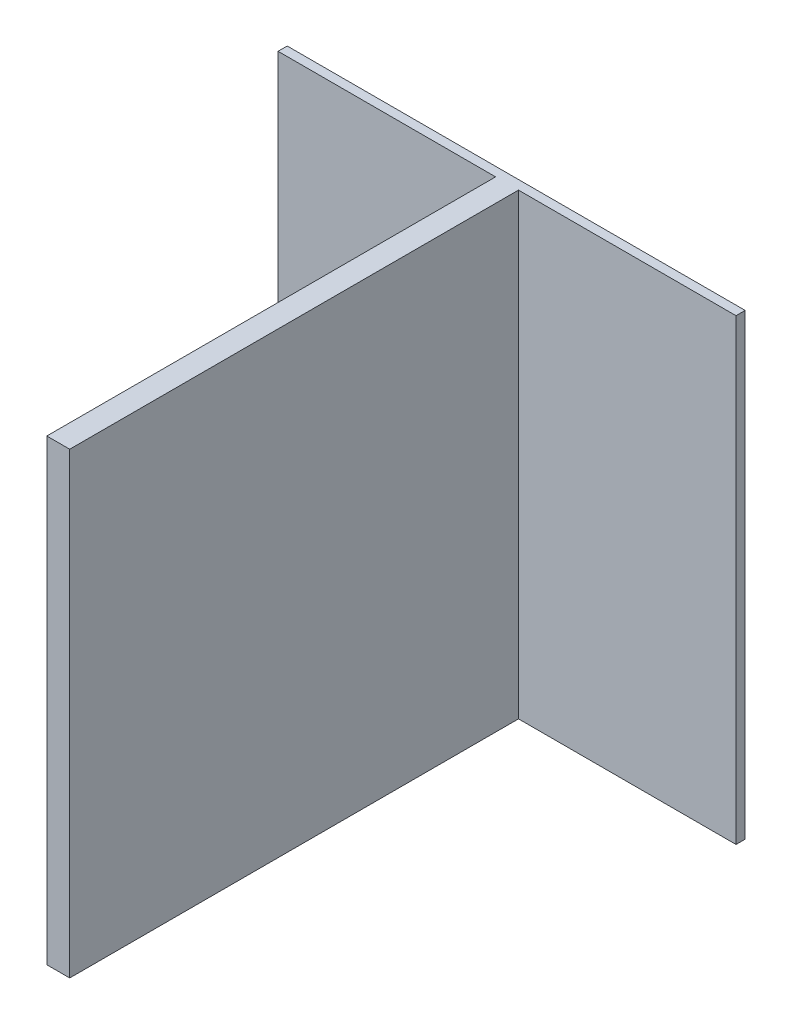
SolidWorks part; units mm, degrees
ref_plane "Płaszczyzna przednia" through (0, 0, 0) normal (0, 0, 1) x (1, 0, 0)
ref_plane "Płaszczyzna górna" through (0, 0, 0) normal (0, 1, 0) x (1, 0, 0)
ref_plane "Płaszczyzna prawa" through (0, 0, 0) normal (1, 0, 0) x (0, 0, -1)
sketch "Szkic1" plane through (0, 0, 0) normal (0, 0, 1) x (1, 0, 0)
  line L0 (0, 0) -> (100, 0)
  line L1 (0, 0) -> (-100, 0)
  line L2 (0, 0) -> (0, 100)
  line L3 (0, 0) -> (0, -100)
  line L4 (0, 100) -> (100, 100)
  line L5 (100, 100) -> (100, 0)
  line L6 (100, -100) -> (0, -100)
  line L7 (100, 0) -> (100, -100)
  line L8 (0, 100) -> (-100, 100)
  line L9 (-100, 100) -> (-100, 0)
  line L10 (-100, -100) -> (-100, 0)
  line L11 (0, -100) -> (-100, -100)
  dimension "D1" = 100
  dimension "D2" = 100
  dimension "D3" = 100
  dimension "D4" = 100
  dimension "D5" = 100
  dimension "D6" = 100
  dimension "D7" = 100
  dimension "D8" = 100
  dimension "D9" = 100
  dimension "D10" = 100
  dimension "D11" = 100
extrude "Dodanie-wyciągnięcie1" add sketch "Szkic1" along normal blind 4 contours L8 L9 L1 L2 | L5 L4 L2 L0 | L7 L0 L3 L6 | L11 L3 L1 L10 region at (50, 50, 0) region at (-50, -50, 0) region at (-50, 50, 0) region at (50, -50, 0)
sketch "Szkic2" plane through (0, 0, 4) normal (0, 0, 1) x (1, 0, 0)
  line L0 (0, 100) -> (0, -100)
  line L1 (100, 100) -> (-100, 100) construction
  line L2 (100, -100) -> (-100, -100) construction
  line L3 (0, 0) -> (5, 0)
  line L4 (0, 0) -> (-5, 0)
  line L5 (5, 0) -> (5, 100)
  line L6 (5, 100) -> (5, -100)
  line L7 (-5, 0) -> (-5, 100)
  line L8 (-5, 0) -> (-5, -100)
  line L9 (-5, -100) -> (5, -100)
  line L10 (5, 100) -> (-5, 100)
  line M9 (-100, -100) -> (100, -100)
  line M11 (100, 100) -> (-100, 100)
  dimension "D1" = 5
  dimension "D2" = 5
  dimension "D3" = 10
  dimension "D4" = 100
  dimension "D5" = 100
  dimension "D6" = 100
  dimension "D7" = 200
  dimension "D8" = 10
extrude "Dodanie-wyciągnięcie2" add sketch "Szkic2" along normal blind 196 contours L7 L4 L0 M11 | L3 L5 L0 M11 | L4 L8 L0 M9 | L6 L3 L0 M9 region at (2.5, 50, 4) region at (-2.5, 50, 4) region at (2.5, -50, 4) region at (-2.5, -50, 4)
